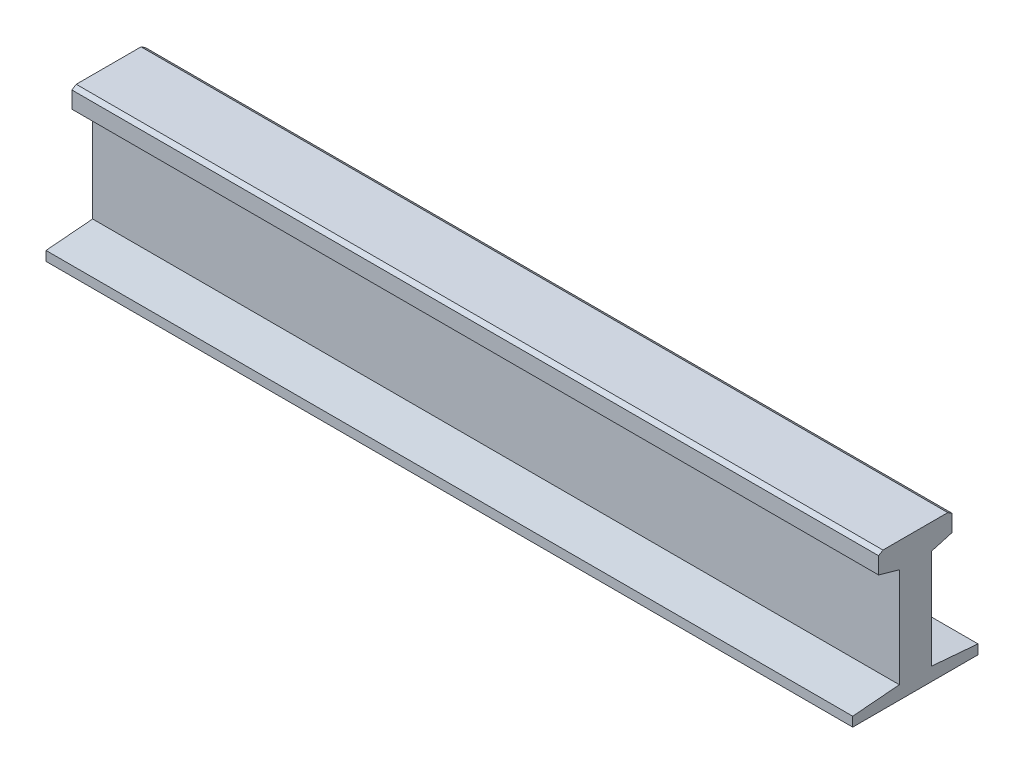
SolidWorks part; units mm, degrees
ref_plane "Спереди" through (0, 0, 0) normal (0, 0, 1) x (1, 0, 0)
ref_plane "Сверху" through (0, 0, 0) normal (0, 1, 0) x (1, 0, 0)
ref_plane "Справа" through (0, 0, 0) normal (1, 0, 0) x (0, 0, -1)
sketch "Эскиз1" plane through (0, 0, 0) normal (1, 0, 0) x (0, 0, -1)
  line L0 (-66, 0) -> (66, 0)
  line L1 (66, 0) -> (66, 10)
  line L2 (66, 10) -> (16.8833, 14.1635)
  line L3 (16.8833, 14.1635) -> (16.8833, 118.9844)
  line L4 (16.8833, 118.9844) -> (38.7045, 125.2191)
  line L5 (-34.151, 145.7096) -> (34.151, 145.7096)
  line L6 (34.151, 145.7096) -> (38.7045, 142.7824)
  line L7 (38.7045, 142.7824) -> (38.7045, 125.2191)
  line L8 (0, 177.3831) -> (0, -45.0863) construction
  line L9 (-38.7045, 142.7824) -> (-38.7045, 125.2191)
  line L10 (-34.151, 145.7096) -> (-38.7045, 142.7824)
  line L11 (-16.8833, 118.9844) -> (-38.7045, 125.2191)
  line L12 (-16.8833, 14.1635) -> (-16.8833, 118.9844)
  line L13 (-66, 10) -> (-16.8833, 14.1635)
  line L14 (-66, 0) -> (-66, 10)
  point P0 (66.0166, 0)
  point P14 (0, 145.7096)
  point P19 (0, 0)
  point P23 (0, 0)
extrude "Бобышка-Вытянуть1" add sketch "Эскиз1" along normal blind 850
